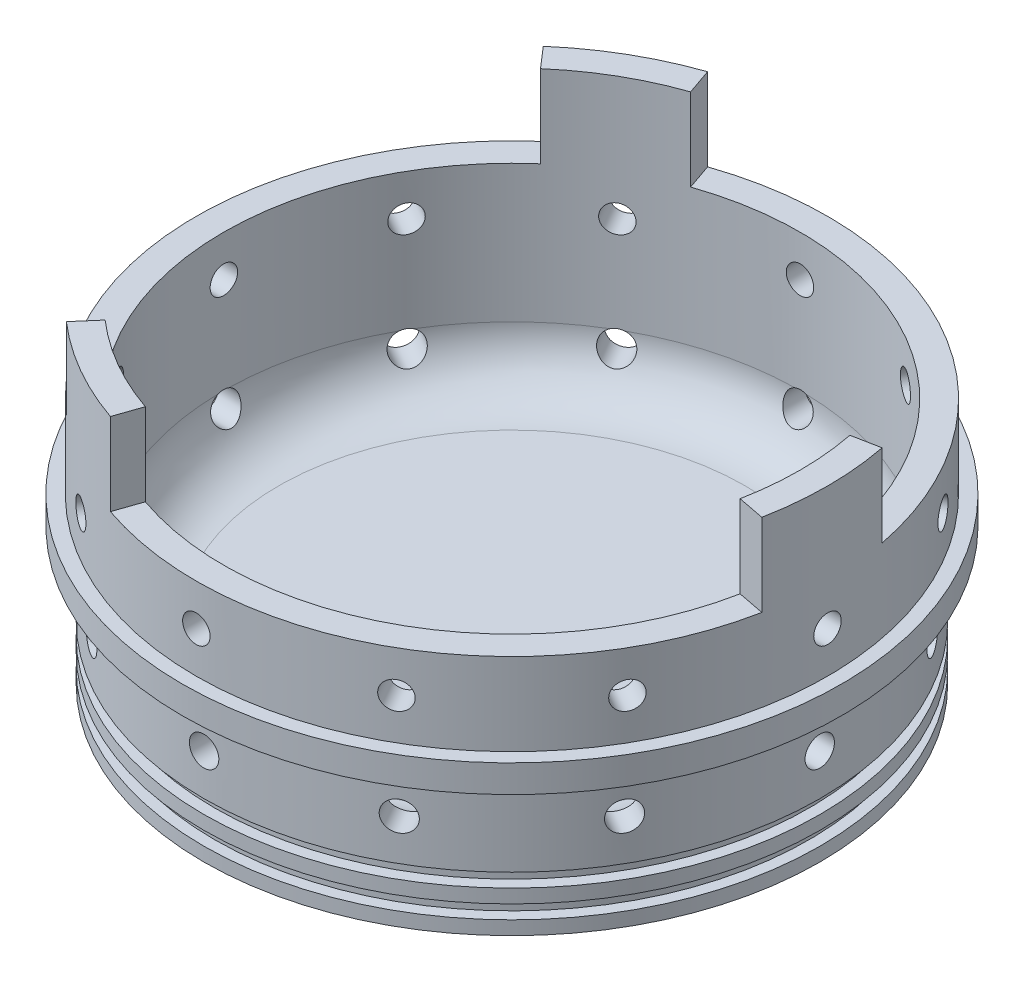
SolidWorks part; units mm, degrees
material "2024-T4"
ref_plane "Front Plane" through (0, 0, 0) normal (0, 0, 1) x (1, 0, 0)
ref_plane "Top Plane" through (0, 0, 0) normal (0, 1, 0) x (1, 0, 0)
ref_plane "Right Plane" through (0, 0, 0) normal (1, 0, 0) x (0, 0, -1)
sketch "Sketch1" plane through (0, 0, 0) normal (0, 1, 0) x (1, 0, 0)
  circle A0 centre (0, 0) radius 76.2
  dimension "D1" = 152.4
extrude "Center Ring(TotOD&Thk)" add sketch "Sketch1" along normal blind 6.35
sketch "Sketch2" plane through (0, 6.35, 0) normal (0, 1, 0) x (1, 0, 0)
  circle A0 centre (0, 0) radius 73.025
  dimension "D1" = 146.05
extrude "Top Ring(AcrylicID&Hgt)" add sketch "Sketch2" along normal blind 38.1
sketch "Sketch3" plane through (0, 0, 0) normal (0, -1, 0) x (1, 0, 0)
  circle A0 centre (0, 0) radius 71.247
  dimension "D1" = 142.494
extrude "Lower Ring(TankID&Depth)" add sketch "Sketch3" along normal blind 31.75
sketch "Sketch4" plane through (0, 44.45, 0) normal (0, 1, 0) x (1, 0, 0)
  circle A0 centre (0, 0) radius 66.675
  circle A1 centre (0, 0) radius 73.025 construction
  circle A2 centre (0, 0) radius 73.025
  dimension "D1" = 133.35
extrude "Bulkhead Hollow(UpperWall&BlkhdThk" cut sketch "Sketch4" against normal offset from surface (63.5 mm away) 12.7 contours A0 up to face at (0, -31.75, -71.247)
sketch "Sketch5" plane through (0, 0, 0) normal (0, 0, 1) x (1, 0, 0)
  line L0 (-71.247, 0) -> (-71.247, -31.75) construction
  line L1 (-71.247, 0) -> (-71.247, -31.75)
  line L2 (-71.247, -28.575) -> (-68.707, -28.575)
  line L3 (-68.707, -28.575) -> (-68.707, -25.4)
  line L4 (-68.707, -25.4) -> (-71.247, -25.4)
  line L5 (-71.247, -22.225) -> (-68.707, -22.225)
  line L6 (-68.707, -22.225) -> (-68.707, -19.05)
  line L7 (-68.707, -19.05) -> (-71.247, -19.05)
  line L8 (-71.247, -31.75) -> (71.247, -31.75) construction
  line L9 (0, 0) -> (0, -31.75) construction
  dimension "D1" = 2.54
  dimension "D2" = 3.175
  dimension "D3" = 3.175
  dimension "D4" = 3.175
  dimension "D5" = 3.175
revolve "O-Ring Channel" cut sketch "Sketch5" angle 360 about L9 region at (-69.977, -20.6375, 0) region at (-69.977, -26.9875, 0)
sketch "Sketch8" plane through (0, 0, 0) normal (0, 0, 1) x (1, 0, 0)
  circle A0 centre (0, -9.525) radius 3.4
  dimension "D1" = 6.8
  dimension "D2" = 9.525
extrude "Lower Bolt Hole (DrillDia&Dist)" cut sketch "Sketch8" along normal through all
pattern_circular "Lower Bolt Hole Ammount" count 12 over 360 about axis through (0, -31.75, 0) along (0, 1, 0) of "Lower Bolt Hole (DrillDia&Dist)" reverse direction yes
sketch "Sketch9" plane through (0, 0, 0) normal (0, 0, 1) x (1, 0, 0)
  line L0 (76.2, 6.35) -> (-76.2, 6.35) construction
  line L1 (76.2, 6.35) -> (-76.2, 6.35)
  circle A0 centre (0, 15.875) radius 3.175
  dimension "D1" = 6.35
  dimension "D2" = 9.525
extrude "Upper Bolt Hole (DrillDia&Dist)" cut sketch "Sketch9" against normal through all contours A0 region at (0, 15.875, 0)
pattern_circular "CirPattern1" count 12 over 360 about axis through (0, 44.45, 0) along (0, -1, 0) of "Upper Bolt Hole (DrillDia&Dist)"
fillet "Smoothing" radius 12.7 1 edges at (0, -19.05, -66.675)
sketch "Sketch10" plane through (0, 44.45, 0) normal (0, 1, 0) x (1, 0, 0)
  line L0 (65.4543, 12.7) -> (71.688, 13.9095)
  line L1 (65.4543, -12.7) -> (71.688, -13.9095)
  line L2 (-21.7286, -63.0351) -> (-23.798, -69.0384)
  line L3 (-43.7257, -50.3351) -> (-47.89, -55.1289)
  line L4 (-43.7257, 50.3351) -> (-47.89, 55.1289)
  line L5 (-21.7286, 63.0351) -> (-23.798, 69.0384)
  circle A0 centre (0, 0) radius 66.675 construction
  circle A1 centre (0, 0) radius 73.025
  circle A2 centre (0, 0) radius 73.025
  circle A3 centre (0, 0) radius 66.675
  point P20 (0, 0)
  circle M5 centre (0, 0) radius 66.675
  circle M6 centre (0, 0) radius 73.025
  dimension "D2" = 25.4
  dimension "D3" = 12.7
extrude "Cut-Extrude1" cut sketch "Sketch10" against normal blind 19.05 contours L5 L0 M5 M6 | L4 L3 M5 M6 | L2 L1 M5 M6 region at (33.9022, 44.45, -58.7204) region at (68.356, 44.45, 14.4135) region at (-67.8158, 44.45, 0)
equation "\"D4@Sketch5\"=\"D2@Sketch5\""
equation "\"D5@Sketch5\"=\"D3@Sketch5\""
equation "\"D3@Sketch10\"=\"D2@Sketch10\"/2"
